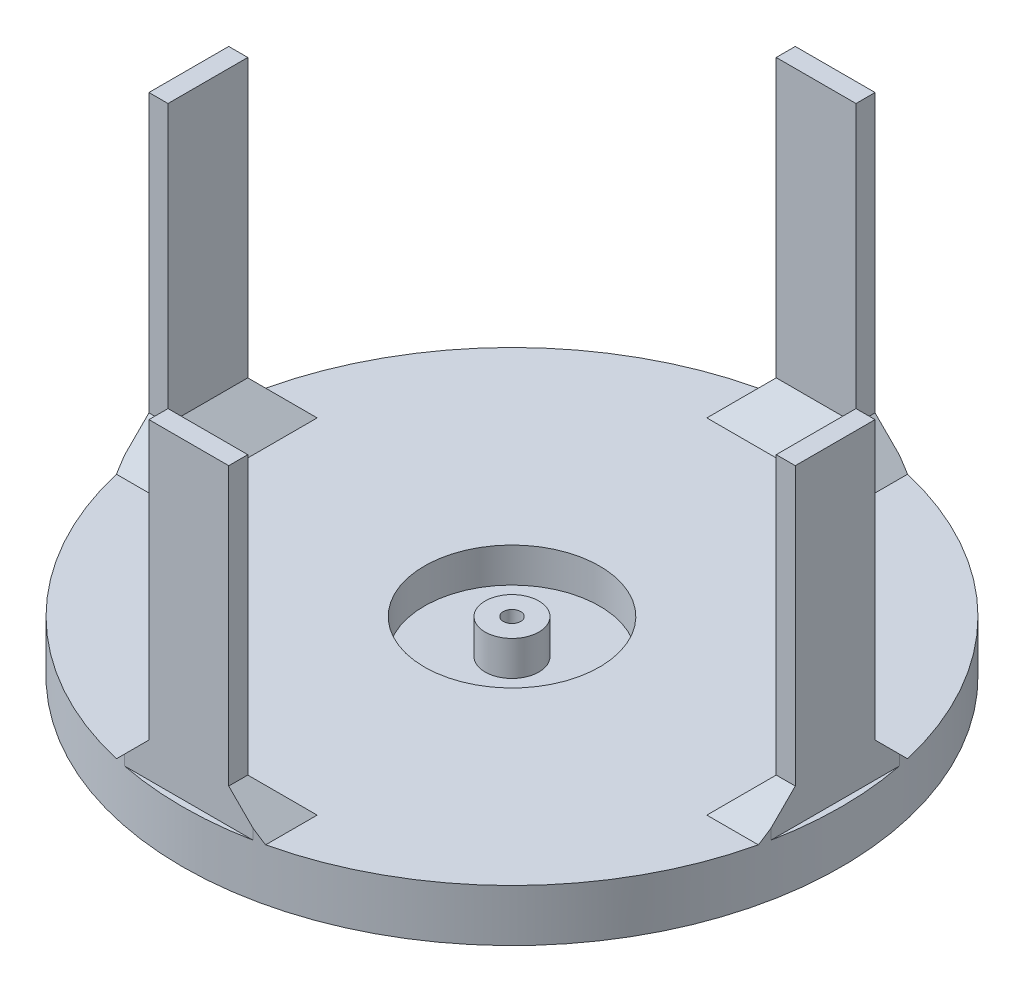
SolidWorks part; units mm, degrees
ref_plane "Front Plane" through (0, 0, 0) normal (0, 0, 1) x (1, 0, 0)
ref_plane "Top Plane" through (0, 0, 0) normal (0, 1, 0) x (1, 0, 0)
ref_plane "Right Plane" through (0, 0, 0) normal (1, 0, 0) x (0, 0, -1)
sketch "Sketch1" plane through (0, 0, 0) normal (0, 1, 0) x (1, 0, 0)
  arc A0 (-9.9861, 94.4737) -> (-86.8097, -38.5886) centre (0, 0) ccw
  arc A1 (-9.9861, 94.4737) -> (9.9861, 94.4737) centre (0, 95) cw construction
  circle A2 centre (0, 95) radius 3 construction
  arc A3 (86.8097, -38.5886) -> (76.8235, -55.8851) centre (82.2724, -47.5) cw construction
  circle A4 centre (82.2724, -47.5) radius 3 construction
  arc A5 (-76.8235, -55.8851) -> (-86.8097, -38.5886) centre (-82.2724, -47.5) cw construction
  circle A6 centre (-82.2724, -47.5) radius 3 construction
  arc A7 (9.9861, 94.4737) -> (-9.9861, 94.4737) centre (0, 0) ccw
  arc A8 (-86.8097, -38.5886) -> (-76.8235, -55.8851) centre (0, 0) ccw
  arc A9 (-76.8235, -55.8851) -> (76.8235, -55.8851) centre (0, 0) ccw
  arc A10 (76.8235, -55.8851) -> (86.8097, -38.5886) centre (0, 0) ccw
  arc A11 (86.8097, -38.5886) -> (9.9861, 94.4737) centre (0, 0) ccw
  point P20 (0, 0)
  dimension "D1" = 190
  dimension "D2" = 10
  dimension "D3" = 6
  dimension "D4" = 95
  dimension "D5" = 3
extrude "Boss-Extrude1" add sketch "Sketch1" along normal mid plane 15
sketch "Sketch2" plane through (0, 7.5, 0) normal (0, 1, 0) x (1, 0, 0)
  line L0 (0, 0) -> (0, 43.602) construction
  line L1 (0, 0) -> (-42.4546, 0) construction
  line L2 (-15, 93.8083) -> (-23.5466, 125.7046) construction
  line L3 (23.5466, 125.7046) -> (15, 93.8083) construction
  line L14 (12.5, 86.674) -> (12.5, 94.174) construction
  line L15 (-12.5, 86.674) -> (-12.5, 94.174) construction
  line L17 (12.5, 86.674) -> (-12.5, 86.674) construction
  line L18 (-12.5, 94.174) -> (12.5, 94.174) construction
  line L31 (-11.5, 93.174) -> (11.5, 93.174)
  line L32 (11.5, 87.674) -> (11.5, 93.174)
  line L33 (11.5, 87.674) -> (-11.5, 87.674)
  line L34 (-11.5, 87.674) -> (-11.5, 93.174)
  line L35 (86.674, 12.5) -> (94.174, 12.5) [skipped]
  line L36 (86.674, -12.5) -> (94.174, -12.5) [skipped]
  line L37 (-86.674, -12.5) -> (-94.174, -12.5) [skipped]
  line L38 (-86.674, 12.5) -> (-94.174, 12.5) [skipped]
  line L39 (12.5, -86.674) -> (12.5, -94.174) [skipped]
  line L40 (-12.5, -86.674) -> (-12.5, -94.174) [skipped]
  line L41 (93.174, 11.5) -> (93.174, -11.5)
  line L42 (87.674, -11.5) -> (93.174, -11.5)
  line L43 (87.674, -11.5) -> (87.674, 11.5)
  line L44 (87.674, 11.5) -> (93.174, 11.5)
  line L45 (11.5, -93.174) -> (-11.5, -93.174)
  line L46 (-11.5, -87.674) -> (-11.5, -93.174)
  line L47 (-11.5, -87.674) -> (11.5, -87.674)
  line L48 (11.5, -87.674) -> (11.5, -93.174)
  line L49 (-93.174, -11.5) -> (-93.174, 11.5)
  line L50 (-87.674, 11.5) -> (-93.174, 11.5)
  line L51 (-87.674, 11.5) -> (-87.674, -11.5)
  line L52 (-87.674, -11.5) -> (-93.174, -11.5)
  circle A0 centre (0, 0) radius 95 construction
  arc A2 (-12.5, 94.174) -> (12.5, 94.174) centre (0, 0) cw construction
  arc A13 (-15, 93.8083) -> (-12.5, 94.174) centre (0, 0) cw construction
  arc A14 (12.5, 94.174) -> (15, 93.8083) centre (0, 0) cw construction
  circle A16 centre (0, 0) radius 95 construction
  arc A17 (94.174, 12.5) -> (94.174, -12.5) centre (0, 0) cw construction
  arc A18 (12.5, -94.174) -> (-12.5, -94.174) centre (0, 0) cw construction
  arc A19 (-94.174, -12.5) -> (-94.174, 12.5) centre (0, 0) cw construction
  point P33 (0, 0)
  point P37 (0, 0)
  point P56 (0, 0)
  dimension "D1" = 7.5
  dimension "D3" = 25
  dimension "D2" = 30
  dimension "D4" = 30
  dimension "D5" = 4
  dimension "D6" = 1
  dimension "D7" = 4
extrude "Boss-Extrude2" add sketch "Sketch2" along normal blind 90
sketch "Sketch3" plane through (0, 7.5, 0) normal (0, 1, 0) x (1, 0, 0)
  circle A0 centre (0, 0) radius 7.75
  circle A1 centre (0, 0) radius 25.25
  dimension "D1" = 15.5
  dimension "D2" = 50.5
extrude "Cut-Extrude1" cut sketch "Sketch3" against normal blind 10
sketch "Sketch4" plane through (0, 7.5, 0) normal (0, 1, 0) x (1, 0, 0)
  circle A0 centre (0, 0) radius 2.5
  dimension "D1" = 5
extrude "Cut-Extrude2" cut sketch "Sketch4" against normal through all both and the other way through all
chamfer "Chamfer1" distance 10 angle 45 12 edges at (-11.5, 7.5, -90.424) (0, 7.5, -87.674) (11.5, 7.5, -90.424) (-90.424, 7.5, -11.5) (-87.674, 7.5, 0) (-90.424, 7.5, 11.5) (-11.5, 7.5, 90.424) (0, 7.5, 87.674) (11.5, 7.5, 90.424) (90.424, 7.5, -11.5) (90.424, 7.5, 11.5) (87.674, 7.5, 0)
